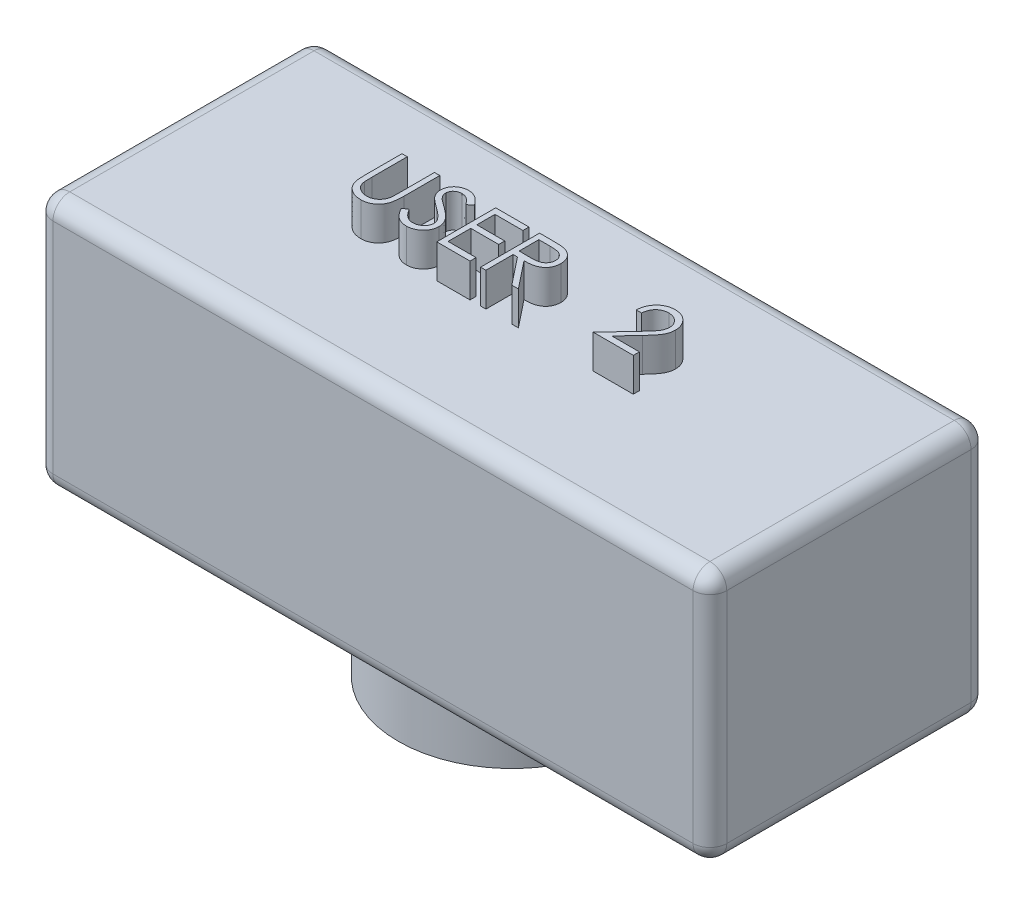
SolidWorks part; units mm, degrees
ref_plane "Front Plane" through (0, 0, 0) normal (0, 0, 1) x (1, 0, 0)
ref_plane "Top Plane" through (0, 0, 0) normal (0, 1, 0) x (1, 0, 0)
ref_plane "Right Plane" through (0, 0, 0) normal (1, 0, 0) x (0, 0, -1)
sketch "Sketch1" plane through (0, 0, 0) normal (0, 1, 0) x (1, 0, 0)
  circle A0 centre (0, 0) radius 5.75
extrude "Boss-Extrude1" add sketch "Sketch1" along normal blind 4.5
sketch "Sketch2" plane through (0, 4.5, 0) normal (0, 1, 0) x (1, 0, 0)
  line L1 (-20, 8.25) -> (20, 8.25)
  line L2 (-20, 8.25) -> (-20, -8.25)
  line L3 (-20, -8.25) -> (20, -8.25)
  line L4 (20, 8.25) -> (20, -8.25)
  line L5 (-20, 8.25) -> (20, -8.25) construction
  line L6 (-20, -8.25) -> (20, 8.25) construction
  point P0 (0, 0)
extrude "Boss-Extrude2" add sketch "Sketch2" along normal blind 15
sketch "Sketch3" plane through (0, 4.5, 0) normal (0, -1, 0) x (1, 0, 0)
  circle A0 centre (0, 0) radius 6.75
extrude "Boss-Extrude3" add sketch "Sketch3" along normal blind 4
sketch "Sketch5" plane through (0, 0, 0) normal (0, -1, 0) x (1, 0, 0)
  circle A0 centre (0, 0) radius 5.75
extrude "Cut-Extrude1" cut sketch "Sketch5" against normal blind 4
fillet "Fillet1" radius 1 4 edges at (20, 19.5, 0) (0, 19.5, 8.25) (-20, 19.5, 0) (0, 19.5, -8.25)
sketch "Sketch9" plane through (0, 19.5, 0) normal (0, 1, 0) x (1, 0, 0)
  text T0 "USER   2" font "Century Gothic" height 3.5
extrude "Boss-Extrude5" add sketch "Sketch9" along normal blind 2
fillet "Fillet2" radius 1 12 edges at (19.7071, 19.2071, -7.9571) (19.7071, 19.2071, 7.9571) (-19.7071, 19.2071, 7.9571) (-19.7071, 19.2071, -7.9571) (0, 4.5, -8.25) (20, 11.5, -8.25) (20, 4.5, 0) (20, 11.5, 8.25) (0, 4.5, 8.25) (-20, 11.5, 8.25) (-20, 4.5, 0) (-20, 11.5, -8.25)
